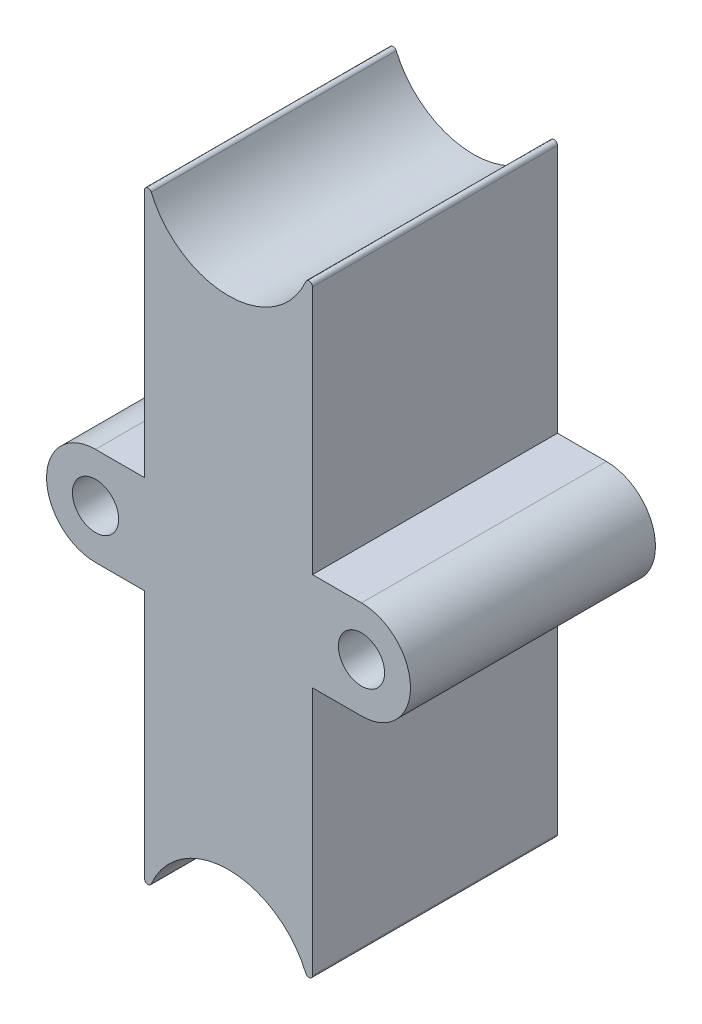
SolidWorks part; units mm, degrees
ref_plane "Front Plane" through (0, 0, 0) normal (0, 0, 1) x (1, 0, 0)
ref_plane "Top Plane" through (0, 0, 0) normal (0, 1, 0) x (1, 0, 0)
ref_plane "Right Plane" through (0, 0, 0) normal (1, 0, 0) x (0, 0, -1)
sketch "Sketch1" plane through (0, 0, 0) normal (0, 0, 1) x (1, 0, 0)
  line L0 (0, 0) -> (-14, 0) construction
  line L1 (-6, -23.75) -> (6, -23.75)
  line L2 (-6, -23.75) -> (-6, 23.75)
  line L3 (-6, 23.75) -> (6, 23.75)
  line L4 (6, -23.75) -> (6, 23.75)
  line L5 (-6, -23.75) -> (6, 23.75) construction
  line L6 (-6, 23.75) -> (6, -23.75) construction
  line L7 (-14, 0) -> (11.9672, 0) construction
  line L8 (-6, 3.5) -> (-9.5, 3.5)
  line L9 (-6, -3.5) -> (-9.5, -3.5)
  line L10 (6, 3.5) -> (9.5, 3.5)
  line L11 (6, -3.5) -> (9.5, -3.5)
  circle A0 centre (0, 23.75) radius 6
  circle A1 centre (0, -23.75) radius 6
  circle A2 centre (9.5, 0) radius 3.5
  circle A3 centre (-9.5, 0) radius 3.5
  circle A4 centre (-9.5, 0) radius 1.65
  circle A5 centre (9.5, 0) radius 1.65
  point P0 (0, 0)
  dimension "D1" = 12
  dimension "D2" = 47.5
extrude "Boss-Extrude1" add sketch "Sketch1" along normal blind 17.5 contours A1 L4 A0 L2 | A3 L2 L8 | A3 L9 L2 | A3 A4 | A2 A5 | A2 L10 L4 | A2 L4 L11 region at (0, 0, 0) region at (-6.7818, -2.7182, 0) region at (6.7818, -2.7182, 0) region at (-6.7818, 2.7182, 0) region at (-7.0951, -2.4049, 0) region at (6.7818, 2.7182, 0) region at (7.0951, 2.4049, 0)
fillet "Fillet1" radius 0.25 4 edges at (-6, -23.75, 8.75) (6, -23.75, 8.75) (6, 23.75, 8.75) (-6, 23.75, 8.75)
